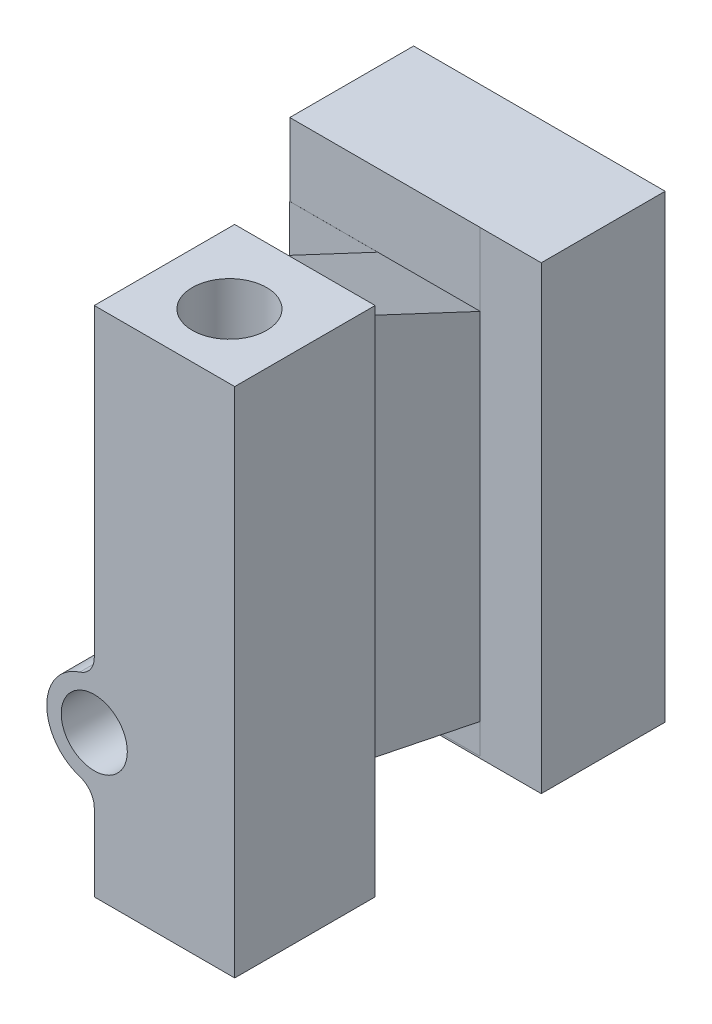
SolidWorks part; units mm, degrees
ref_plane "Front Plane" through (0, 0, 0) normal (0, 0, 1) x (1, 0, 0)
ref_plane "Top Plane" through (0, 0, 0) normal (0, 1, 0) x (1, 0, 0)
ref_plane "Right Plane" through (0, 0, 0) normal (1, 0, 0) x (0, 0, -1)
sketch "Sketch1" plane through (0, 0, 0) normal (0, 0, 1) x (1, 0, 0)
  line L1 (-22.1812, 49.3094) -> (11.8188, 49.3094)
  line L2 (-22.1812, 49.3094) -> (-22.1812, -74.6906)
  line L3 (-22.1812, -74.6906) -> (11.8188, -74.6906)
  line L4 (11.8188, 49.3094) -> (11.8188, -74.6906)
  dimension "D1" = 124
  dimension "D2" = 34
extrude "Boss-Extrude1" add sketch "Sketch1" along normal blind 34
sketch "Sketch2" plane through (0, 0, 34) normal (0, 0, 1) x (1, 0, 0)
  line L0 (-22.1812, 49.3094) -> (-22.1812, -74.6906) construction
  circle A0 centre (-22.1812, -40.2508) radius 11.504
extrude "Boss-Extrude2" add sketch "Sketch2" against normal blind 34
fillet "Fillet1" radius 5 2 edges at (-22.1812, -51.7548, 17) (-22.1812, -28.7468, 17)
sketch "Sketch3" plane through (0, -74.6906, 0) normal (0, -1, 0) x (1, 0, 0)
  circle A0 centre (-4.8936, 17.1062) radius 13.5862
extrude "Cut-Extrude1" cut sketch "Sketch3" against normal blind 50
sketch "Sketch4" plane through (0, 0, 34) normal (0, 0, 1) x (1, 0, 0)
  circle A0 centre (-22.1812, -40.2508) radius 8
  arc A1 (-25.6665, -29.2874) -> (-25.6665, -51.2142) centre (-22.1812, -40.2508) ccw construction
extrude "Cut-Extrude2" cut sketch "Sketch4" against normal blind 20
sketch "Sketch5" plane through (0, 0, 0) normal (0, 0, -1) x (-1, 0, 0)
  line L1 (-7.2618, 48.6909) -> (17.5691, 48.6909)
  line L2 (-7.2618, 48.6909) -> (-7.2618, -62.513)
  line L3 (-7.2618, -62.513) -> (17.5691, -62.513)
  line L4 (17.5691, 48.6909) -> (17.5691, -62.513)
extrude "Boss-Extrude3" add sketch "Sketch5" along normal blind 30
sketch "Sketch6" plane through (0, 0, -30) normal (0, 0, -1) x (-1, 0, 0)
  line L1 (-22.0319, 48.3699) -> (38.868, 48.3699)
  line L2 (-22.0319, 48.3699) -> (-22.0319, -62.9411)
  line L3 (-22.0319, -62.9411) -> (38.868, -62.9411)
  line L4 (38.868, 48.3699) -> (38.868, -62.9411)
extrude "Boss-Extrude4" add sketch "Sketch6" along normal blind 30
sketch "Sketch7" plane through (0, 49.3094, 0) normal (0, 1, 0) x (1, 0, 0)
  circle A0 centre (-5.0915, -18.3589) radius 8.9987
extrude "Cut-Extrude3" cut sketch "Sketch7" against normal blind 100
sketch "Sketch9" plane through (7.2618, 0, 0) normal (1, 0, 0) x (0, 0, -1)
  line L0 (-0.0119, 53.1584) -> (-0.0119, 44.8625)
  line L1 (-0.0119, 44.8625) -> (30.0187, 30.7835)
  line L2 (30.0187, 30.7835) -> (30.0187, 53.1584)
  line L3 (30.0187, 53.1584) -> (-0.0119, 53.1584)
  line L4 (-0.0119, -49.0284) -> (-0.0119, -66.3738)
  line L5 (-0.0119, -66.3738) -> (29.9948, -69.2814)
  line L6 (29.9948, -69.2814) -> (29.9948, -55.1732)
  line L7 (29.9948, -55.1732) -> (-0.0119, -49.0284)
extrude "Cut-Extrude5" cut sketch "Sketch9" against normal blind 100
